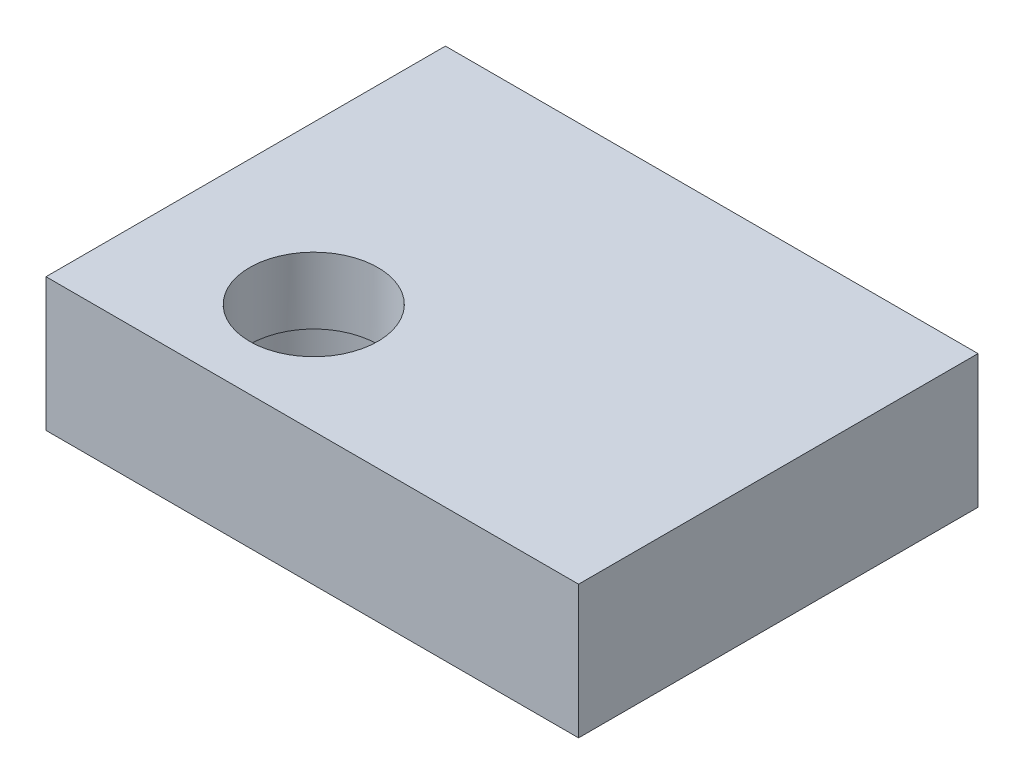
SolidWorks part; units mm, degrees
material "PLA"
ref_plane "Front Plane" through (0, 0, 0) normal (0, 0, 1) x (1, 0, 0)
ref_plane "Top Plane" through (0, 0, 0) normal (0, 1, 0) x (1, 0, 0)
ref_plane "Right Plane" through (0, 0, 0) normal (1, 0, 0) x (0, 0, -1)
sketch "Sketch1" plane through (0, 0, 0) normal (0, 1, 0) x (1, 0, 0)
  line L1 (-20, -15) -> (20, -15)
  line L2 (-20, -15) -> (-20, 15)
  line L3 (-20, 15) -> (20, 15)
  line L4 (20, -15) -> (20, 15)
  line L5 (-20, -15) -> (20, 15) construction
  line L6 (-20, 15) -> (20, -15) construction
  point P0 (0, 0)
  dimension "D1" = 40
  dimension "D2" = 30
extrude "Boss-Extrude1" add sketch "Sketch1" along normal blind 10
sketch "Sketch2" plane through (0, 0, 0) normal (0, -1, 0) x (-1, 0, 0)
  line L0 (20, 15) -> (-20, -15) construction
  line L1 (20, -15) -> (-20, 15) construction
  line L2 (20, -15) -> (-20, -15) construction
  line L3 (20, 0) -> (-20, 0) construction
  line L4 (20, 15) -> (20, -15) construction
  line L5 (-20, -15) -> (-20, 15) construction
  line L6 (0, -15) -> (0, 15) construction
  line L7 (-20, 15) -> (20, 15) construction
  circle A0 centre (-13.3333, -10) radius 2
  circle A1 centre (-13.3333, 10) radius 2
  circle A2 centre (13.3333, 10) radius 2
  circle A3 centre (8.14, -6.75) radius 6.3
  dimension "D1" = 4
  dimension "D5" = 12.6
  dimension "D2" = 5
  dimension "D3" = 11.86
  dimension "D4" = 8.25
extrude "Cut-Extrude1" cut sketch "Sketch2" against normal blind 5
sketch "Sketch3" plane through (0, 10, 0) normal (0, 1, 0) x (1, 0, 0)
  line L6 (-20, 15) -> (-20, -15) construction
  line L10 (-20, -15) -> (20, -15) construction
  circle A0 centre (-8.14, -6.75) radius 4.8125
  dimension "D1" = 9.625
  dimension "D2" = 11.86
  dimension "D3" = 8.25
extrude "Cut-Extrude2" cut sketch "Sketch3" against normal up to surface (10 mm away) up to face at (-8.14, 0, 0.45)
